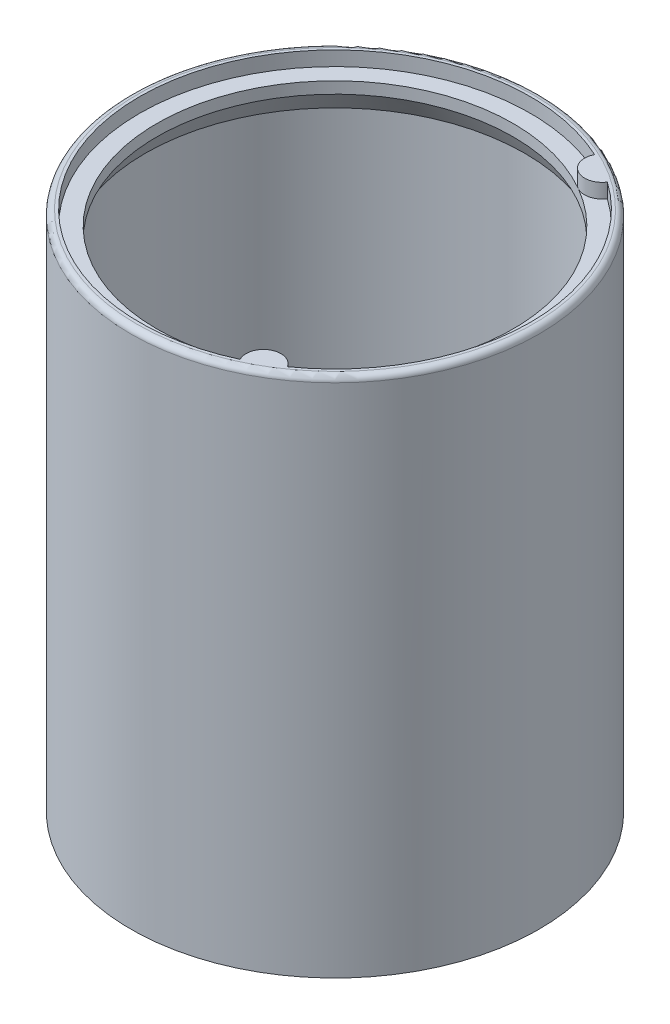
SolidWorks part; units mm, degrees
ref_plane "Plan de face" through (0, 0, 0) normal (0, 0, 1) x (1, 0, 0)
ref_plane "Plan de dessus" through (0, 0, 0) normal (0, 1, 0) x (1, 0, 0)
ref_plane "Plan de droite" through (0, 0, 0) normal (1, 0, 0) x (0, 0, -1)
sketch "Esquisse1" plane through (0, 0, 0) normal (0, 1, 0) x (1, 0, 0)
  circle A0 centre (0, 0) radius 35.25
  dimension "D1" = 70.5
extrude "Boss.-Extru.1" add sketch "Esquisse1" along normal blind 90
fillet "Congé1" radius 1 1 edges at (0, 90, 35.25)
sketch "Esquisse4" plane through (0, 90, 0) normal (0, 1, 0) x (1, 0, 0)
  circle A0 centre (0, 0) radius 33.75
  circle A1 centre (0, 0) radius 35.25 construction
  circle A2 centre (0, 0) radius 35.25
  dimension "D1" = 1.5
  dimension "D2" = 70.5
extrude "Enlèv. mat.-Extru.3" cut sketch "Esquisse4" against normal blind 2.5 contours A0
sketch "Esquisse5" plane through (0, 87.5, 0) normal (0, 1, 0) x (1, 0, 0)
  circle A0 centre (0, 0) radius 32.75
  circle A1 centre (0, 0) radius 33.75
  circle A2 centre (0, 0) radius 33.75
  dimension "D2" = 1
  dimension "D1" = 0
extrude "Enlèv. mat.-Extru.4" cut sketch "Esquisse5" against normal blind 84 contours A0 region at (0, 87.5, 0)
sketch "Esquisse6" plane through (0, 87.5, 0) normal (0, 1, 0) x (1, 0, 0)
  circle A0 centre (0, 0) radius 30.75
  circle A1 centre (0, 0) radius 33.75
  circle A2 centre (0, 0) radius 33.75
  circle A4 centre (0, 0) radius 32.75 construction
  dimension "D2" = 2
  dimension "D1" = 0
extrude "Boss.-Extru.2" add sketch "Esquisse6" against normal blind 10
chamfer "Chanfrein1" distance 8 angle 30 1 edges at (0, 77.5, 30.75) first distance on face at (0, 77.5, 30.75)
sketch "Esquisse7" plane through (0, 87.5, 0) normal (0, 1, 0) x (1, 0, 0)
  line L0 (-35.9633, 0) -> (35.25, 0) construction
  circle A0 centre (0, 0) radius 35.25 construction
  circle A1 centre (0, 0) radius 33.75
  circle A2 centre (0, 0) radius 33.75
  arc A3 (-33.6167, 2.997) -> (-33.6167, -2.997) centre (-33.75, 0) cw
  arc A4 (19.4038, 27.6144) -> (14.2128, 30.6114) centre (16.875, 29.2284) cw
  arc A5 (14.2128, -30.6114) -> (19.4038, -27.6144) centre (16.875, -29.2284) cw
  point P19 (0, 0)
  circle M2 centre (0, 0) radius 33.75
  dimension "D2" = 3
  dimension "D1" = 0
  dimension "D3" = 3
extrude "Boss.-Extru.3" add sketch "Esquisse7" along normal blind 2.5 contours A4 M2 | A5 M2 region at (16.2265, 87.5, -28.1052) region at (16.2265, 87.5, 28.1052)
sketch "Esquisse8" plane through (0, 3.5, 0) normal (0, 1, 0) x (1, 0, 0)
  circle A0 centre (0, 0) radius 6.2
  dimension "D1" = 12.4
extrude "Boss.-Extru.4" add sketch "Esquisse8" along normal blind 8
sketch "Esquisse2" plane through (0, 0, 0) normal (0, -1, 0) x (1, 0, 0)
  circle A0 centre (0, 0) radius 3.2
  dimension "D1" = 6.4
extrude "Enlèv. mat.-Extru.1" cut sketch "Esquisse2" against normal through all
fillet "Congé2" radius 1.5 3 edges at (0, 3.5, 6.2) (0, 11.5, 6.2) (0, 3.5, 32.75)
